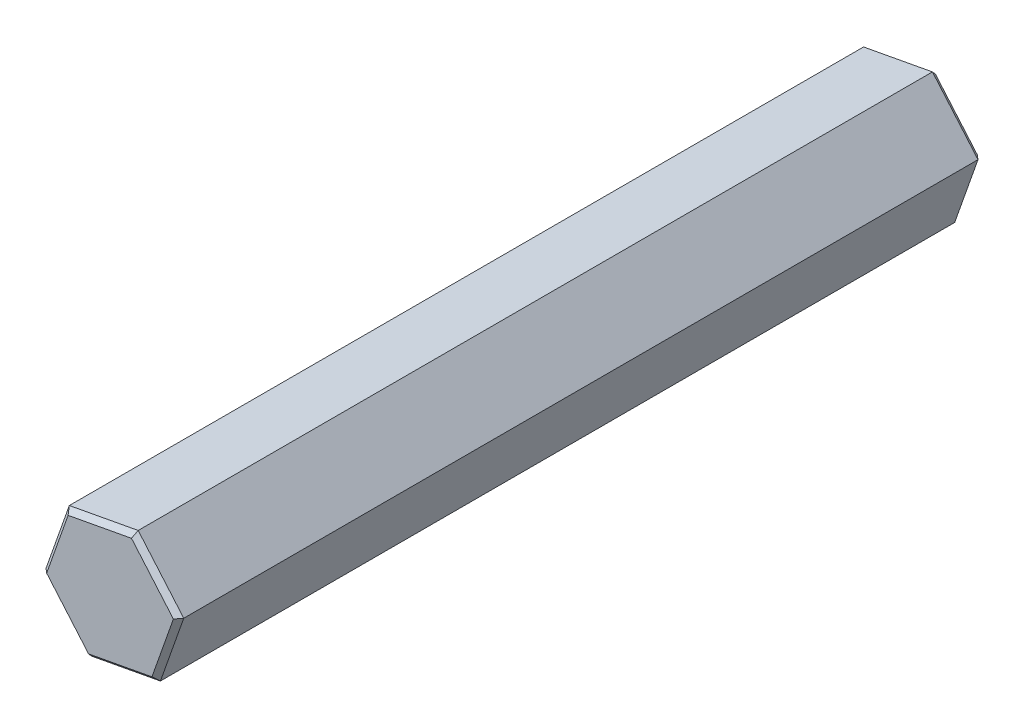
SolidWorks part; units mm, degrees
ref_plane "Front Plane" through (0, 0, 0) normal (0, 0, 1) x (1, 0, 0)
ref_plane "Top Plane" through (0, 0, 0) normal (0, 1, 0) x (1, 0, 0)
ref_plane "Right Plane" through (0, 0, 0) normal (1, 0, 0) x (0, 0, -1)
sketch "Sketch1" plane through (0, 0, 0) normal (0, 0, 1) x (1, 0, 0)
  line L1 (-2.4404, -6.9143) -> (4.7678, -5.5706)
  line L2 (4.7678, -5.5706) -> (7.2082, 1.3438)
  line L3 (7.2082, 1.3438) -> (2.4404, 6.9143)
  line L4 (2.4404, 6.9143) -> (-4.7678, 5.5706)
  line L5 (-4.7678, 5.5706) -> (-7.2082, -1.3438)
  line L6 (-7.2082, -1.3438) -> (-2.4404, -6.9143)
  circle A0 centre (0, 0) radius 6.35 construction
  dimension "D1" = 12.7
extrude "Boss-Extrude1" add sketch "Sketch1" along normal mid plane 84.1375
chamfer "Chamfer2" distance 0.508 angle 45 6 edges at (-5.988, 2.1134, -42.0688) (-4.8243, -4.129, -42.0688) (1.1637, -6.2425, -42.0688) (5.988, -2.1134, -42.0688) (4.8243, 4.129, -42.0688) (-1.1637, 6.2425, -42.0688)
chamfer "Chamfer3" distance 0.508 angle 45 6 edges at (-5.988, 2.1134, 42.0688) (-4.8243, -4.129, 42.0688) (1.1637, -6.2425, 42.0688) (5.988, -2.1134, 42.0688) (-1.1637, 6.2425, 42.0688) (4.8243, 4.129, 42.0688)
